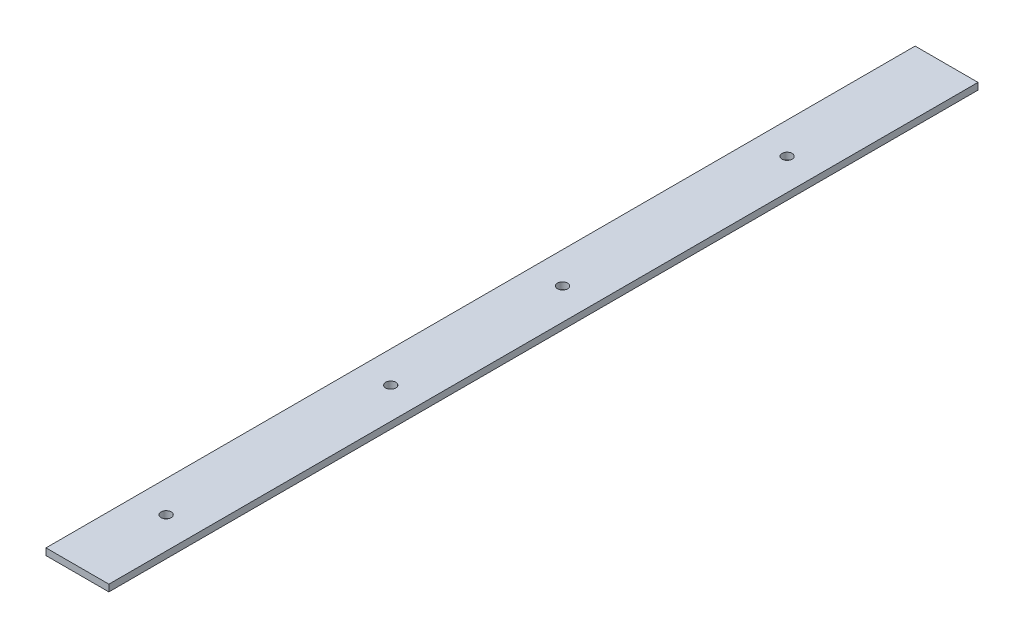
SolidWorks part; units mm, degrees
ref_plane "Front Plane" through (0, 0, 0) normal (0, 0, 1) x (1, 0, 0)
ref_plane "Top Plane" through (0, 0, 0) normal (0, 1, 0) x (1, 0, 0)
ref_plane "Right Plane" through (0, 0, 0) normal (1, 0, 0) x (0, 0, -1)
sketch "Sketch1" plane through (0, 0, 0) normal (0, 1, 0) x (1, 0, 0)
  line L1 (-14, -193.5) -> (14, -193.5)
  line L2 (-14, -193.5) -> (-14, 193.5)
  line L3 (-14, 193.5) -> (14, 193.5)
  line L4 (14, -193.5) -> (14, 193.5)
  line L5 (-14, -193.5) -> (14, 193.5) construction
  line L6 (-14, 193.5) -> (14, -193.5) construction
  point P0 (0, 0)
  dimension "D1" = 387
  dimension "D2" = 28
extrude "Boss-Extrude1" add sketch "Sketch1" along normal blind 3
hole_wizard "M4 Clearance Hole1" positions "Sketch2" profile "Sketch3" hole size "M4" standard "ANSI Metric" end condition through all
sketch "Sketch2" plane through (0, 3, 0) normal (0, 1, 0) x (1, 0, 0)
  line L0 (0, -154) -> (0, -54)
  line L1 (-14, -193.5) -> (14, -193.5) construction
  point P1 (0, -154)
  point P2 (0, -54)
  dimension "D1" = 100
  dimension "D2" = 39.5
sketch "Sketch3" plane through (0, 3, 154) normal (1, 0, 0) x (0, 0, 1)
  line L0 (0, 0) -> (0, 3)
  line L1 (0, 3) -> (2.25, 3)
  line L2 (2.25, 3) -> (2.25, 0)
  line L5 (2.25, 0) -> (0, 0)
  line L11 (0, -6.35) -> (0, 107.95) construction
  dimension "Thru Hole Dia." = 4.5
  dimension "Thru Hole Depth" = 3
pattern_linear "LPattern2" count 2 spacing 176.5 along (0, 0, -1) of "M4 Clearance Hole1"
